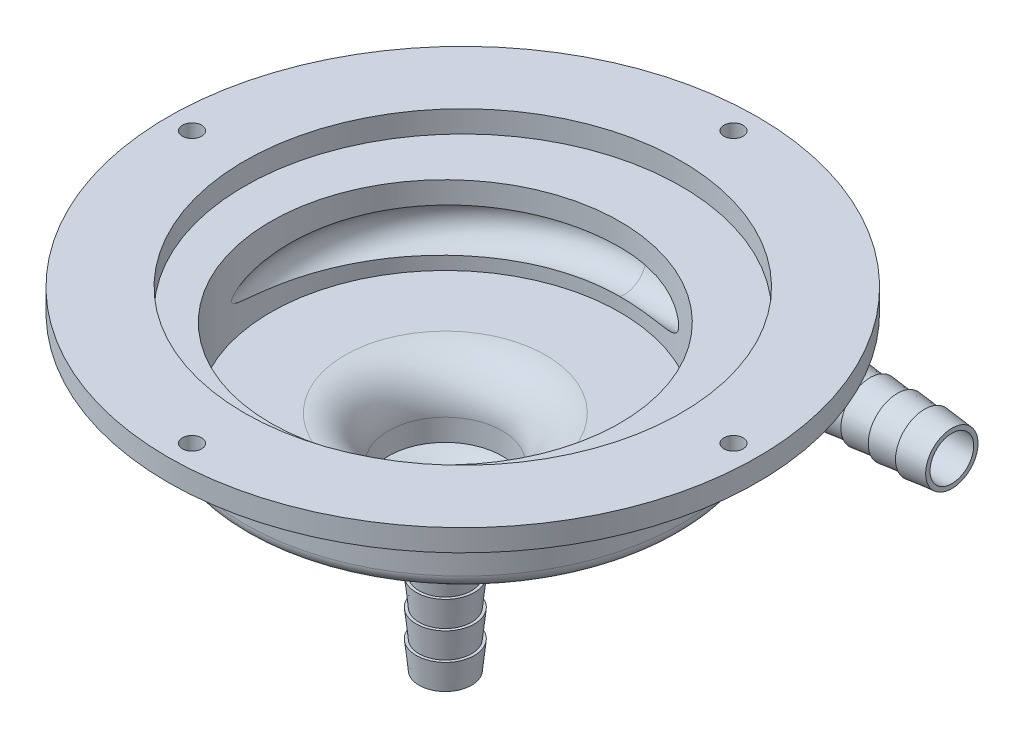
SolidWorks part; units mm, degrees
material "PLA"
ref_plane "Front Plane" through (0, 0, 0) normal (0, 0, 1) x (1, 0, 0)
ref_plane "Top Plane" through (0, 0, 0) normal (0, 1, 0) x (1, 0, 0)
ref_plane "Right Plane" through (0, 0, 0) normal (1, 0, 0) x (0, 0, -1)
sketch "Sketch1" plane through (0, 0, 0) normal (0, 1, 0) x (1, 0, 0)
  circle A0 centre (0, 0) radius 50
  circle A1 centre (0, -4) radius 40
  dimension "D1" = 4
  dimension "D2" = 80
extrude "Boss-Extrude1" add sketch "Sketch1" along normal blind 20
sketch "Sketch2" plane through (0, 0, 0) normal (0, 1, 0) x (1, 0, 0)
  circle A0 centre (0, 0) radius 50
  circle A1 centre (0, -4) radius 40
  dimension "D1" = 4
extrude "Boss-Extrude2" add sketch "Sketch2" along normal blind 2 and the other way blind 4 contours A1
sketch "Sketch3" plane through (0, 20, 0) normal (0, 1, 0) x (1, 0, 0)
  circle A0 centre (0, 0) radius 50
  circle A1 centre (0, 0) radius 67.5
  circle A2 centre (0, 62) radius 2.2
  circle A3 centre (62, 0) radius 2.2
  circle A4 centre (0, -62) radius 2.2
  circle A5 centre (-62, 0) radius 2.2
  point P15 (0, 0)
  dimension "D1" = 62
  dimension "D3" = 135
  dimension "D2" = 4
extrude "Boss-Extrude3" add sketch "Sketch3" along normal blind 5 separate body
ref_plane "Plane1" through (50, 0, 0) normal (1, 0, 0) x (0, 0, -1)
sketch "Sketch4" plane through (50, 0, 0) normal (1, 0, 0) x (0, 0, -1)
  line L0 (0, 0) -> (0, 36.7589) construction
  circle A2 centre (37, 10) radius 6
  circle A3 centre (37, 10) radius 4.75
  dimension "D1" = 12
  dimension "D2" = 9.5
  dimension "D5" = 37
  dimension "D6" = 10
  dimension "D3" = 10
  dimension "D4" = 37
sketch "Sketch5" plane through (0, 0, 0) normal (0, 1, 0) x (1, 0, 0)
  line L1 (0, 0) -> (66.027, 0) construction
  line L3 (50, 37) -> (19.8565, 37)
sweep "Sweep1" add profiles "Sketch4" path "Sketch5"
sketch "Sketch6" plane through (0, 0, 0) normal (0, 1, 0) x (1, 0, 0)
  line L1 (50, -11) -> (50, 11) construction
  line L2 (50, 41) -> (50, 64.0091) construction
  line L3 (50, 41) -> (0, 41)
  arc A1 (0, 41) -> (-20.2102, -34.4256) centre (0, 0.5795) ccw
  dimension "D1" = 40.4205
  dimension "D2" = 20.2102
  dimension "D3" = 0.5795
sketch "Sketch7" plane through (50, 0, 0) normal (1, 0, 0) x (0, 0, -1)
  circle A2 centre (37, 10) radius 5
  dimension "D1" = 10
sweep "Cut-Sweep4" cut profiles "Sketch7" path "Sketch6"
sketch "Sketch9" plane through (0, -4, 0) normal (0, -1, 0) x (1, 0, 0)
  circle A0 centre (0, 4) radius 15
  circle A3 centre (0, 4) radius 40 construction
extrude "Boss-Extrude5" add sketch "Sketch9" along normal blind 15
sketch "Sketch10" plane through (0, -19, 0) normal (0, -1, 0) x (1, 0, 0)
  circle A0 centre (0, 4) radius 5.5
  circle A1 centre (0, 4) radius 15 construction
extrude "Boss-Extrude6" add sketch "Sketch10" along normal blind 5
sketch "Sketch11" plane through (0, -24, 0) normal (0, -1, 0) x (1, 0, 0)
  circle A0 centre (0, 4) radius 4.5
extrude "Cut-Extrude1" cut sketch "Sketch11" against normal through all
sketch "Sketch12" plane through (0, 2, 0) normal (0, 1, 0) x (1, 0, 0)
  circle A0 centre (0, -4) radius 13
  circle A1 centre (0, -4) radius 4.5 construction
extrude "Cut-Extrude2" cut sketch "Sketch12" against normal blind 15
fillet "Fillet1" radius 10 2 edges at (0, -13, 8.5) (0, 2, 17)
fillet "Fillet2" radius 3 3 edges at (0, -19, -11) (0, 0, 50) (0, -4, 44)
ref_plane "Plane2" through (0, 0, -37) normal (0, 0, 1) x (1, 0, 0)
sketch "Sketch13" plane through (0, 0, -37) normal (0, 0, 1) x (1, 0, 0)
  line L0 (50, 10) -> (83.6068, 10) construction
  line L1 (50, 10) -> (50, 4)
  line L2 (75, 4) -> (75, 10)
  line L3 (75, 10) -> (50, 10)
  line L4 (50, 3.35) -> (50, 4)
  line L5 (56.25, 4) -> (50, 3.35)
  line L6 (56.25, 3.35) -> (56.25, 4)
  line L7 (62.5, 4) -> (56.25, 3.35)
  line L8 (62.5, 3.35) -> (62.5, 4)
  line L9 (68.75, 4) -> (62.5, 3.35)
  line L10 (68.75, 3.35) -> (68.75, 4)
  line L11 (75, 4) -> (68.75, 3.35)
  line L12 (50, 4) -> (50, 16) construction
  point P13 (50, 10)
  point P16 (50.5038, 10)
  dimension "D1" = 6
  dimension "D2" = 25
  dimension "D3" = 6.25
  dimension "D4" = 0.65
  dimension "D5" = 6
  dimension "D6" = 95.937
  dimension "D7" = 18.75
  dimension "D8" = 12.5
  dimension "D9" = 12.5
  dimension "D10" = 0.65
  dimension "D11" = 6.25
  dimension "D12" = 6
  dimension "D13" = 6
  dimension "D14" = 6.65
  dimension "D15" = 6.65
revolve "Revolve1" add sketch "Sketch13" angle 360 about L0
sketch "Sketch14" plane through (75, 0, 0) normal (1, 0, 0) x (0, 0, -1)
  circle A0 centre (37, 10) radius 5
  dimension "D1" = 10
extrude "Cut-Extrude3" cut sketch "Sketch14" against normal up to next (25 mm away)
ref_plane "Plane3" through (0, 0, 4) normal (0, 0, 1) x (1, 0, 0)
sketch "Sketch15" plane through (0, 0, 4) normal (0, 0, 1) x (1, 0, 0)
  line L0 (-5.5, -24) -> (5.5, -24) construction
  point P0 (0, -34)
  line B0 (0, 24.1623) -> (0, -29.5345) construction
  line B1 (0, -24) -> (-6, -24)
  line B2 (-6, -49) -> (0, -49)
  line B3 (0, -49) -> (0, -24)
  line B4 (-6.65, -24) -> (-6, -24)
  line B5 (-6, -30.25) -> (-6.65, -24)
  line B6 (-6.65, -30.25) -> (-6, -30.25)
  line B7 (-6, -36.5) -> (-6.65, -30.25)
  line B8 (-6.65, -36.5) -> (-6, -36.5)
  line B9 (-6, -42.75) -> (-6.65, -36.5)
  line B10 (-6.65, -42.75) -> (-6, -42.75)
  line B11 (-6, -49) -> (-6.65, -42.75)
sketch_block_instance "Block1-1"
sketch_block "Block1" parameters "D1"=6, "D2"=25, "D3"=6.25, "D4"=0.65, "D5"=6, "D6"=95.937, "D7"=18.75, "D8"=12.5, "D9"=12.5, "D10"=0.65, "D11"=6.25, "D12"=6, "D13"=6, "D14"=6.65, "D15"=6.65
revolve "Revolve2" add sketch "Sketch15" angle 360 about L0
sketch "Sketch16" plane through (0, -49, 0) normal (0, -1, 0) x (1, 0, 0)
  circle A0 centre (0, 4) radius 5
  dimension "D1" = 10
extrude "Cut-Extrude4" cut sketch "Sketch16" against normal up to next
